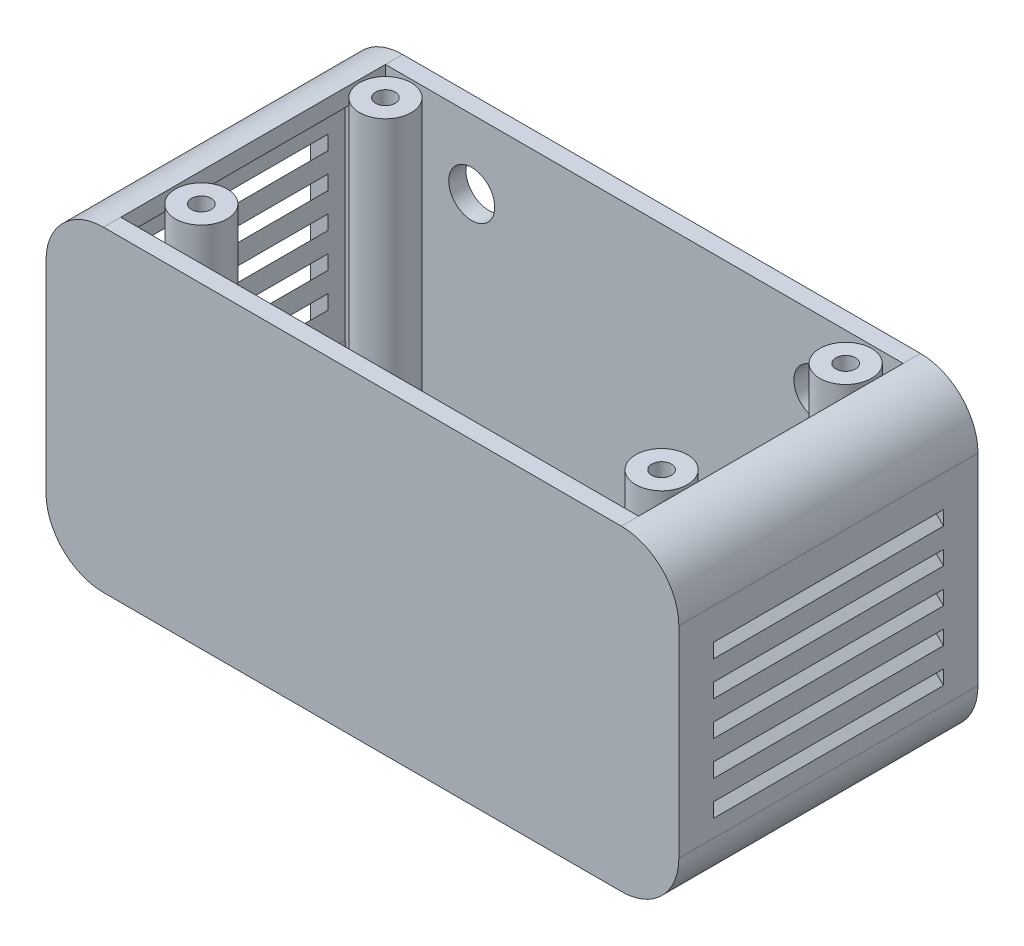
SolidWorks part; units mm, degrees
material "ABS"
ref_plane "Front Plane" through (0, 0, 0) normal (0, 0, 1) x (1, 0, 0)
ref_plane "Top Plane" through (0, 0, 0) normal (0, 1, 0) x (1, 0, 0)
ref_plane "Right Plane" through (0, 0, 0) normal (1, 0, 0) x (0, 0, -1)
sketch "Sketch1" plane through (0, 0, 0) normal (0, 0, 1) x (1, 0, 0)
  line L0 (-45, -55) -> (45, -55)
  line L1 (55, -45) -> (55, -10)
  line L2 (45, 0) -> (-45, 0)
  line L3 (-55, -10) -> (-55, -45)
  arc A0 (45, -55) -> (55, -45) centre (45, -45) ccw
  arc A1 (55, -10) -> (45, 0) centre (45, -10) ccw
  arc A2 (-45, 0) -> (-55, -10) centre (-45, -10) ccw
  arc A3 (-55, -45) -> (-45, -55) centre (-45, -45) ccw
extrude "Boss-Extrude1" add sketch "Sketch1" along normal blind 52
shell "Shell1" thickness 3 removed face at (0, 0, 26)
sketch "Sketch2" plane through (0, 0, 0) normal (0, 1, 0) x (1, 0, 0)
  circle A0 centre (-40, -8) radius 4.5
  circle A1 centre (40, -8) radius 4.5
  circle A2 centre (-40, -40) radius 4.5
  circle A3 centre (40, -40) radius 4.5
extrude "Boss-Extrude2" add sketch "Sketch2" against normal blind 52
sketch "Sketch3" plane through (0, -55, 0) normal (0, -1, 0) x (1, 0, 0)
  circle A0 centre (-40, 8) radius 3.25
  circle A1 centre (40, 8) radius 3.25
  circle A2 centre (-40, 40) radius 3.25
  circle A3 centre (40, 40) radius 3.25
extrude "Cut-Extrude1" cut sketch "Sketch3" against normal blind 49
sketch "Sketch4" plane through (0, -6, 0) normal (0, -1, 0) x (1, 0, 0)
  circle A0 centre (-40, 8) radius 1.7
  circle A1 centre (40, 8) radius 1.7
  circle A2 centre (-40, 40) radius 1.7
  circle A3 centre (40, 40) radius 1.7
extrude "Cut-Extrude2" cut sketch "Sketch4" against normal through all
ref_plane "Plane1" through (0, 0, 26) normal (0, 0, 1) x (1, 0, 0)
sketch "Sketch5" plane through (0, 0, 26) normal (0, 0, 1) x (1, 0, 0)
  line L0 (-51, -14) -> (-51, -11.5)
  line L1 (-51, -11.5) -> (-55.5, -16)
  line L2 (-55.5, -16) -> (-55.5, -18.5)
  line L3 (-55.5, -18.5) -> (-51, -14)
  line L4 (51, -14) -> (51, -11.5)
  line L5 (51, -11.5) -> (55.5, -16)
  line L6 (55.5, -16) -> (55.5, -18.5)
  line L7 (55.5, -18.5) -> (51, -14)
  line L8 (-51, -20) -> (-51, -17.5)
  line L9 (-51, -17.5) -> (-55.5, -22)
  line L10 (-55.5, -22) -> (-55.5, -24.5)
  line L11 (-55.5, -24.5) -> (-51, -20)
  line L12 (51, -20) -> (51, -17.5)
  line L13 (51, -17.5) -> (55.5, -22)
  line L14 (55.5, -22) -> (55.5, -24.5)
  line L15 (55.5, -24.5) -> (51, -20)
  line L16 (-51, -26) -> (-51, -23.5)
  line L17 (-51, -23.5) -> (-55.5, -28)
  line L18 (-55.5, -28) -> (-55.5, -30.5)
  line L19 (-55.5, -30.5) -> (-51, -26)
  line L20 (51, -26) -> (51, -23.5)
  line L21 (51, -23.5) -> (55.5, -28)
  line L22 (55.5, -28) -> (55.5, -30.5)
  line L23 (55.5, -30.5) -> (51, -26)
  line L24 (-51, -32) -> (-51, -29.5)
  line L25 (-51, -29.5) -> (-55.5, -34)
  line L26 (-55.5, -34) -> (-55.5, -36.5)
  line L27 (-55.5, -36.5) -> (-51, -32)
  line L28 (51, -32) -> (51, -29.5)
  line L29 (51, -29.5) -> (55.5, -34)
  line L30 (55.5, -34) -> (55.5, -36.5)
  line L31 (55.5, -36.5) -> (51, -32)
  line L32 (-51, -38) -> (-51, -35.5)
  line L33 (-51, -35.5) -> (-55.5, -40)
  line L34 (-55.5, -40) -> (-55.5, -42.5)
  line L35 (-55.5, -42.5) -> (-51, -38)
  line L36 (51, -38) -> (51, -35.5)
  line L37 (51, -35.5) -> (55.5, -40)
  line L38 (55.5, -40) -> (55.5, -42.5)
  line L39 (55.5, -42.5) -> (51, -38)
extrude "Cut-Extrude3" cut sketch "Sketch5" against normal blind 20 and the other way blind 20
sketch "Sketch6" plane through (0, -55, 0) normal (0, -1, 0) x (1, 0, 0)
  line L0 (-33, 12) -> (-33, 40) construction
  line L1 (-34.5, 12) -> (-34.5, 40)
  line L2 (-31.5, 12) -> (-31.5, 40)
  line L3 (-27, 12) -> (-27, 40) construction
  line L4 (-28.5, 12) -> (-28.5, 40)
  line L5 (-25.5, 12) -> (-25.5, 40)
  line L6 (-21, 12) -> (-21, 40) construction
  line L7 (-22.5, 12) -> (-22.5, 40)
  line L8 (-19.5, 12) -> (-19.5, 40)
  line L9 (-15, 12) -> (-15, 40) construction
  line L10 (-16.5, 12) -> (-16.5, 40)
  line L11 (-13.5, 12) -> (-13.5, 40)
  line L12 (-9, 12) -> (-9, 40) construction
  line L13 (-10.5, 12) -> (-10.5, 40)
  line L14 (-7.5, 12) -> (-7.5, 40)
  line L15 (-3, 12) -> (-3, 40) construction
  line L16 (-4.5, 12) -> (-4.5, 40)
  line L17 (-1.5, 12) -> (-1.5, 40)
  line L18 (3, 12) -> (3, 40) construction
  line L19 (1.5, 12) -> (1.5, 40)
  line L20 (4.5, 12) -> (4.5, 40)
  line L21 (9, 12) -> (9, 40) construction
  line L22 (7.5, 12) -> (7.5, 40)
  line L23 (10.5, 12) -> (10.5, 40)
  line L24 (33, 12) -> (33, 40) construction
  line L25 (31.5, 12) -> (31.5, 40)
  line L26 (34.5, 12) -> (34.5, 40)
  arc A0 (-34.5, 12) -> (-31.5, 12) centre (-33, 12) ccw
  arc A1 (-31.5, 40) -> (-34.5, 40) centre (-33, 40) ccw
  arc A2 (-28.5, 12) -> (-25.5, 12) centre (-27, 12) ccw
  arc A3 (-25.5, 40) -> (-28.5, 40) centre (-27, 40) ccw
  arc A4 (-22.5, 12) -> (-19.5, 12) centre (-21, 12) ccw
  arc A5 (-19.5, 40) -> (-22.5, 40) centre (-21, 40) ccw
  arc A6 (-16.5, 12) -> (-13.5, 12) centre (-15, 12) ccw
  arc A7 (-13.5, 40) -> (-16.5, 40) centre (-15, 40) ccw
  arc A8 (-10.5, 12) -> (-7.5, 12) centre (-9, 12) ccw
  arc A9 (-7.5, 40) -> (-10.5, 40) centre (-9, 40) ccw
  arc A10 (-4.5, 12) -> (-1.5, 12) centre (-3, 12) ccw
  arc A11 (-1.5, 40) -> (-4.5, 40) centre (-3, 40) ccw
  arc A12 (1.5, 12) -> (4.5, 12) centre (3, 12) ccw
  arc A13 (4.5, 40) -> (1.5, 40) centre (3, 40) ccw
  arc A14 (7.5, 12) -> (10.5, 12) centre (9, 12) ccw
  arc A15 (10.5, 40) -> (7.5, 40) centre (9, 40) ccw
  arc A16 (31.5, 12) -> (34.5, 12) centre (33, 12) ccw
  arc A17 (34.5, 40) -> (31.5, 40) centre (33, 40) ccw
  point P2 (-33, 26)
  point P7 (-27, 26)
  point P14 (-21, 26)
  point P21 (-15, 26)
  point P28 (-9, 26)
  point P35 (-3, 26)
  point P42 (3, 26)
  point P49 (9, 26)
  point P56 (33, 26)
  point P63 (0, 0)
extrude "Cut-Extrude4" cut sketch "Sketch6" against normal blind 3.5
sketch "Sketch7" plane through (0, 0, 0) normal (0, 0, -1) x (-1, 0, 0)
  circle A0 centre (30, -12) radius 4
  circle A1 centre (-30, -12) radius 4
extrude "Cut-Extrude5" cut sketch "Sketch7" against normal blind 3.5
sketch "Sketch8" plane through (0, -52, 0) normal (0, 1, 0) x (1, 0, 0)
  line L0 (-30.25, -26) -> (30.25, -26) construction
  line L1 (-47, -36) -> (-41, -36)
  line L2 (-47, -36) -> (-47, -16)
  line L3 (-47, -16) -> (-41, -16)
  line L4 (-41, -36) -> (-41, -16)
  line L5 (-47, -36) -> (-41, -16) construction
  line L6 (-47, -16) -> (-41, -36) construction
  point P0 (-44, -26)
extrude "Boss-Extrude3" add sketch "Sketch8" along normal blind 8
sketch "Sketch9" plane through (0, -44, 0) normal (0, 1, 0) x (1, 0, 0)
  line L0 (-30.25, -26) -> (30.25, -26) construction
  line L1 (-44.95, -34.3) -> (-43.05, -34.3)
  line L2 (-44.95, -34.3) -> (-44.95, -17.7)
  line L3 (-44.95, -17.7) -> (-43.05, -17.7)
  line L4 (-43.05, -34.3) -> (-43.05, -17.7)
  line L5 (-44.95, -34.3) -> (-43.05, -17.7) construction
  line L6 (-44.95, -17.7) -> (-43.05, -34.3) construction
  point P0 (-44, -26)
extrude "Cut-Extrude6" cut sketch "Sketch9" against normal blind 6
sketch "Sketch10" plane through (0, -55, 0) normal (0, -1, 0) x (1, 0, 0)
  circle A0 centre (20, 26) radius 5
extrude "Cut-Extrude7" cut sketch "Sketch10" against normal blind 3.5
